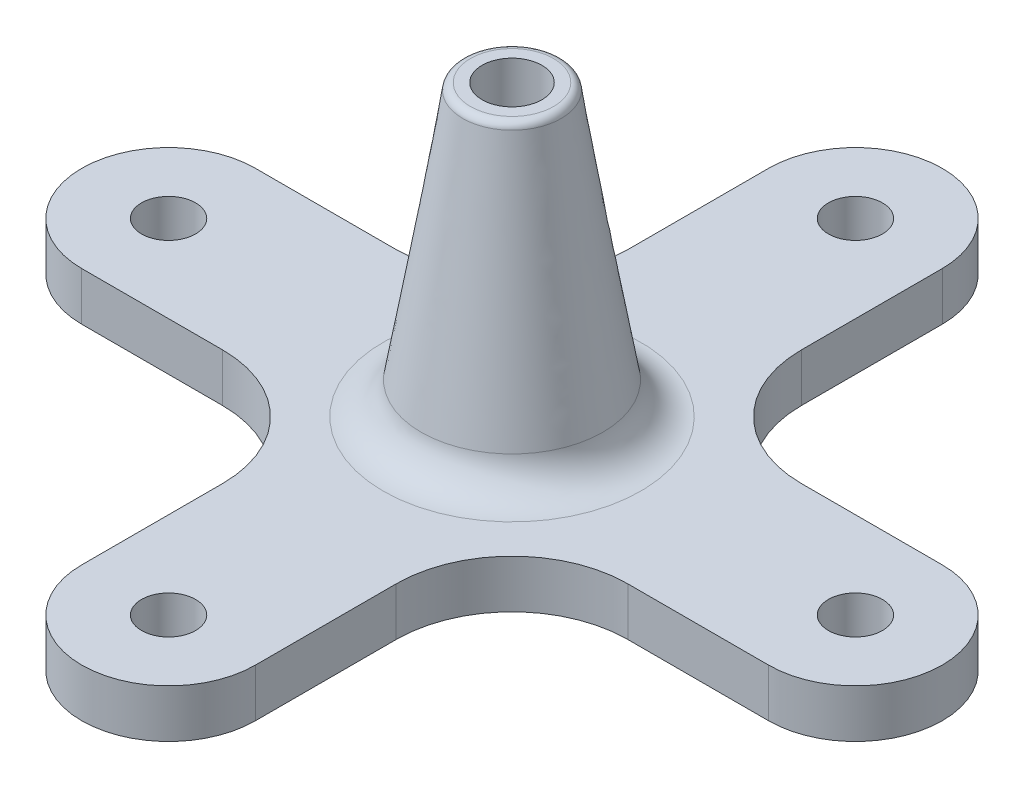
SolidWorks part; units mm, degrees
material "ABS"
ref_plane "Front Plane" through (0, 0, 0) normal (0, 0, 1) x (1, 0, 0)
ref_plane "Top Plane" through (0, 0, 0) normal (0, 1, 0) x (1, 0, 0)
ref_plane "Right Plane" through (0, 0, 0) normal (1, 0, 0) x (0, 0, -1)
sketch "Sketch1" plane through (0, 0, 0) normal (0, 1, 0) x (1, 0, 0)
  line L0 (-22.606, 0) -> (22.606, 0) construction
  line L1 (-22.606, 5.08) -> (22.606, 5.08)
  line L2 (-22.606, -5.08) -> (22.606, -5.08)
  line L3 (0, -22.606) -> (0, 22.606) construction
  line L4 (-5.08, -22.606) -> (-5.08, 22.606)
  line L5 (5.08, -22.606) -> (5.08, 22.606)
  line L6 (-22.606, 5.715) -> (22.606, 5.715)
  line L7 (-22.606, -5.715) -> (22.606, -5.715)
  line L8 (-5.715, -22.606) -> (-5.715, 22.606)
  line L9 (5.715, -22.606) -> (5.715, 22.606)
  arc A0 (-22.606, 5.08) -> (-22.606, -5.08) centre (-22.606, 0) ccw
  arc A1 (22.606, -5.08) -> (22.606, 5.08) centre (22.606, 0) ccw
  arc A2 (-5.08, -22.606) -> (5.08, -22.606) centre (0, -22.606) ccw
  arc A3 (5.08, 22.606) -> (-5.08, 22.606) centre (0, 22.606) ccw
  arc A4 (22.606, -5.715) -> (22.606, 5.715) centre (22.606, 0) ccw
  arc A5 (-22.606, 5.715) -> (-22.606, -5.715) centre (-22.606, 0) ccw
  arc A6 (5.715, 22.606) -> (-5.715, 22.606) centre (0, 22.606) ccw
  arc A7 (-5.715, -22.606) -> (5.715, -22.606) centre (0, -22.606) ccw
  point P2 (0, 0)
  point P10 (0, 0)
  dimension "D2" = 5.08
  dimension "D4" = 5.08
  dimension "D1" = 22.606
  dimension "D3" = 22.606
  dimension "D5" = 0.635
extrude "Boss-Extrude1" add sketch "Sketch1" along normal blind 3.175 contours L9 A6 L8 A7 | L7 A4 L6 A5
fillet "Fillet1" radius 7.62 4 edges at (5.715, 1.5875, 5.715) (5.715, 1.5875, -5.715) (-5.715, 1.5875, -5.715) (-5.715, 1.5875, 5.715)
sketch "Sketch2" plane through (0, 3.175, 0) normal (0, 1, 0) x (1, 0, 0)
  circle A0 centre (0, 0) radius 6.35
  dimension "D1" = 12.7
ref_plane "Plane1" through (0, 22.225, 0) normal (0, 1, 0) x (1, 0, 0)
sketch "Sketch3" plane through (0, 22.225, 0) normal (0, 1, 0) x (1, 0, 0)
  circle A0 centre (0, 0) radius 3.175
  dimension "D1" = 6.35
loft "Loft1" add profiles "Sketch2", "Sketch3" connector at (-2.8651, 3.175, -5.6669) connector at (-2.2703, 22.225, -2.2195)
fillet "Fillet2" radius 2.54 1 edges at (0, 3.175, 6.35)
sketch "Sketch4" plane through (0, 22.225, 0) normal (0, 1, 0) x (1, 0, 0)
  circle A0 centre (0, 0) radius 1.9685
  dimension "D1" = 3.937
extrude "Cut-Extrude1" cut sketch "Sketch4" against normal up to surface (19.05 mm away) up to face at (0, 3.175, 8.4839)
fillet "Fillet3" radius 0.508 1 edges at (0, 22.225, 3.175)
sketch "Sketch6" plane through (0, 3.175, 0) normal (0, 1, 0) x (1, 0, 0)
  line L0 (22.606, 0) -> (-22.606, 0)
  line L1 (0, -22.606) -> (0, 22.606)
  circle A1 centre (-22.606, 0) radius 1.778
  circle A2 centre (22.606, 0) radius 1.778
  circle A3 centre (0, 22.606) radius 1.778
  circle A4 centre (0, -22.606) radius 1.778
  point P7 (0, 0)
  point P10 (0, 0)
  point P18 (0, 0)
  dimension "D1" = 3.556
  dimension "D2" = 3.556
  dimension "D3" = 3.556
  dimension "D4" = 3.556
extrude "Cut-Extrude2" cut sketch "Sketch6" against normal up to surface (3.175 mm away) contours A1 | A4 | A2 | A3 region at (1.2217, 3.175, 21.3843) region at (-24.3337, 3.175, 0) up to face at (0, 0, 0)
